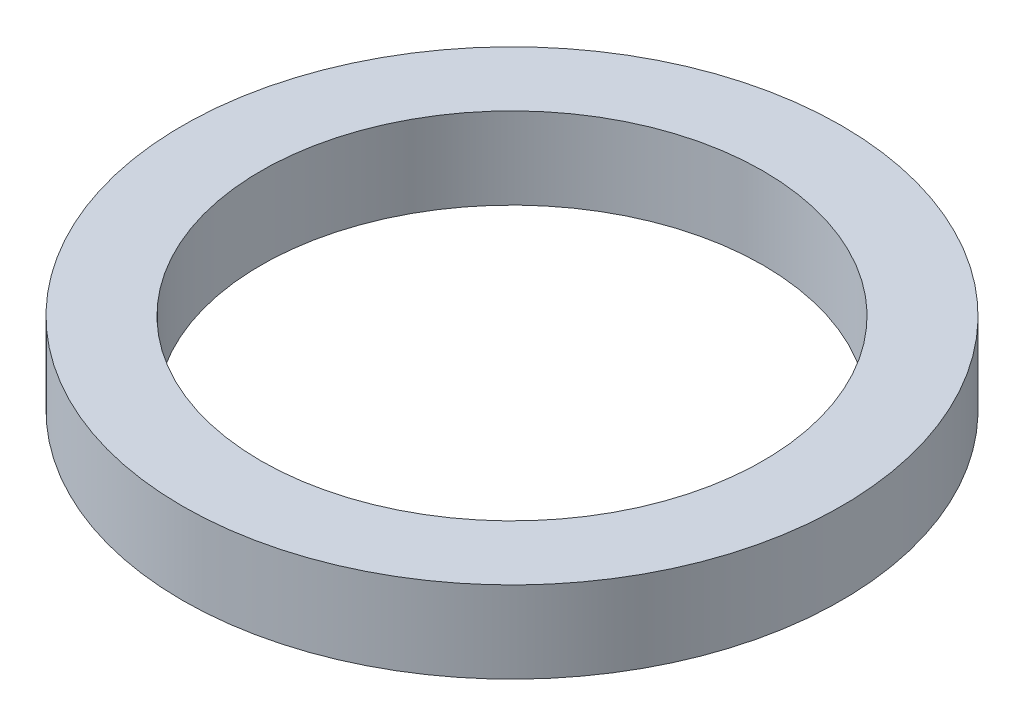
SolidWorks part; units mm, degrees
ref_plane "Front Plane" through (0, 0, 0) normal (0, 0, 1) x (1, 0, 0)
ref_plane "Top Plane" through (0, 0, 0) normal (0, 1, 0) x (1, 0, 0)
ref_plane "Right Plane" through (0, 0, 0) normal (1, 0, 0) x (0, 0, -1)
sketch "Sketch1" plane through (0, 0, 0) normal (0, 1, 0) x (1, 0, 0)
  circle A0 centre (0, 0) radius 52.5
  dimension "FLANGE_OD" = 105
extrude "Boss-Extrude1" add sketch "Sketch1" along normal blind 13
sketch "Sketch2" plane through (0, 0, 0) normal (0, 1, 0) x (1, 0, 0)
  circle A0 centre (0, 0) radius 40
  dimension "BORE_D" = 80
extrude "Cut-Extrude1" cut sketch "Sketch2" along normal through all
sketch "Sketch3" plane through (0, 13, 0) normal (0, 1, 0) x (1, 0, 0)
  circle A0 centre (0, 0) radius 21.3773 construction
  circle A1 centre (-21.3773, 0) radius 1.6237
  dimension "BOLT_D" = 3.2473
  dimension "BOLT_PCD" = 42.7546
extrude "Cut-Extrude2" cut sketch "Sketch3" against normal blind 11.8953 rebuild error yes
pattern_circular "CirPattern1" count 8 over 360 rebuild error yes
